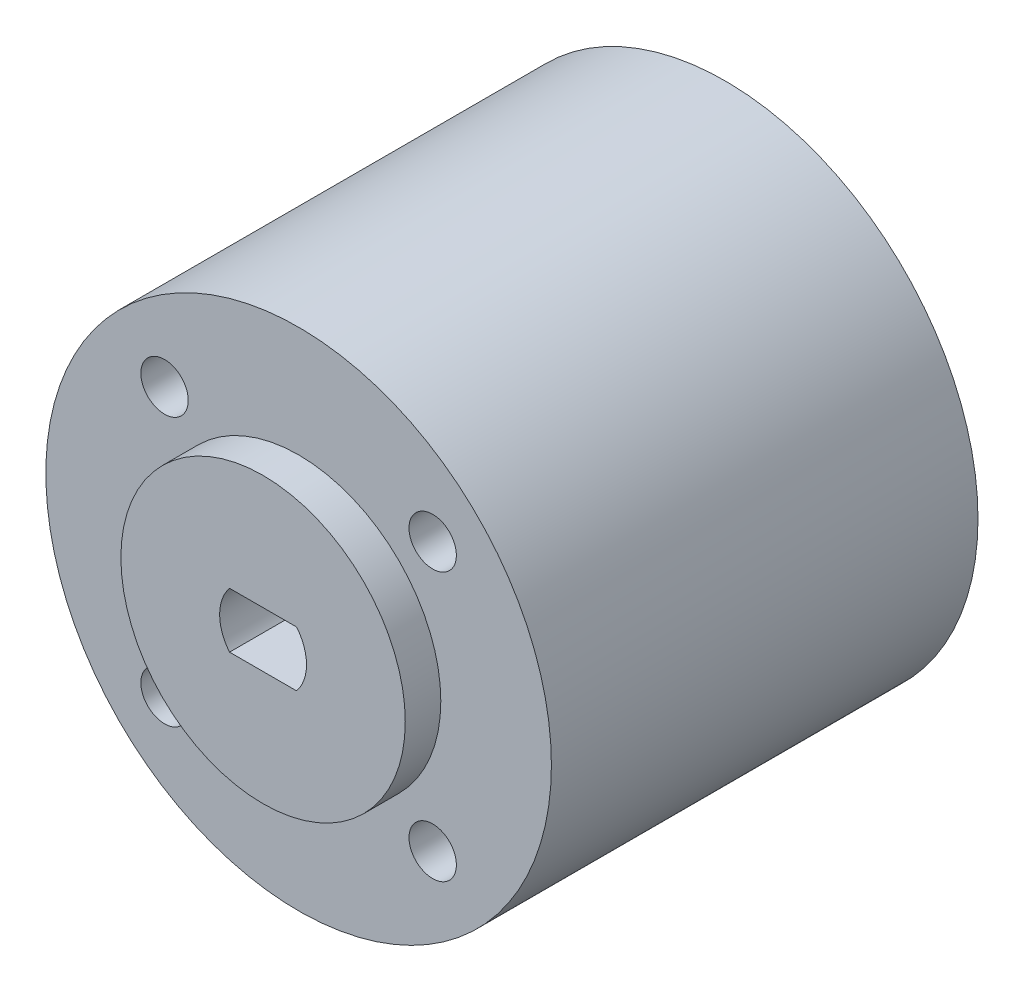
SolidWorks part; units mm, degrees
ref_plane "Front Plane" through (0, 0, 0) normal (0, 0, 1) x (1, 0, 0)
ref_plane "Top Plane" through (0, 0, 0) normal (0, 1, 0) x (1, 0, 0)
ref_plane "Right Plane" through (0, 0, 0) normal (1, 0, 0) x (0, 0, -1)
sketch "Sketch1" plane through (0, 0, 0) normal (0, 0, 1) x (1, 0, 0)
  line L0 (0, 0) -> (0, 19.4252) construction
  line L1 (0, 0) -> (-8.4853, 8.4853) construction
  circle A0 centre (0, 0) radius 16
  circle A1 centre (0, 0) radius 12 construction
  circle A2 centre (0, 0) radius 7.5
  circle A3 centre (-8.4853, 8.4853) radius 1.5
  circle A4 centre (8.4853, 8.4853) radius 1.5
  circle A5 centre (8.4853, -8.4853) radius 1.5
  circle A6 centre (-8.4853, -8.4853) radius 1.5
  circle A8 centre (0, 0) radius 9
  point P17 (0, 0)
  dimension "D1" = 32
  dimension "D2" = 24
  dimension "D3" = 15
  dimension "D5" = 3
  dimension "D7" = 18
  dimension "D4" = 45
  dimension "D6" = 4
extrude "Boss-Extrude3" add sketch "Sketch1" along normal mid plane 27 contours A0 A8 A6 A5 A4 A3 region at (-15.5475, 0, 0)
extrude "Boss-Extrude4" add sketch "Sketch1<6>" along normal mid plane 31.5 contours A2 | A8
sketch "Sketch1<6>" plane through (0, 0, 0) normal (0, 0, 1) x (1, 0, 0) same geometry as "Sketch1"
sketch "Sketch2" plane through (0, 0, 15.75) normal (0, 0, 1) x (1, 0, 0)
  line L3 (-2.1213, 1.75) -> (2.1213, 1.75)
  line L5 (0, 2.75) -> (1.4528, 2.3349) construction
  line L6 (-1.4528, 2.3349) -> (0, 2.75) construction
  line L7 (-2.1213, -1.75) -> (2.1213, -1.75)
  line L11 (0, -2.75) -> (1.4528, -2.3349) construction
  line L12 (-1.4528, -2.3349) -> (0, -2.75) construction
  circle A0 centre (0, 0) radius 7.5
  circle A1 centre (0, 0) radius 2.75
  point P4 (0, 2.75)
  circle M3 centre (0, 0) radius 7.5
  dimension "D1" = 5.5
  dimension "D2" = 3.5
extrude "Boss-Extrude6" add sketch "Sketch2" along direction (0, 0, 1) on the side against the normal up to surface (31.5 mm away) contours A1 M3 | L3 A1 | L7 A1 region at (0, 2.157, 15.75) region at (0, -2.157, 15.75) region at (-7.2879, 0, 15.75) up to face at (9, 0, -15.75)
